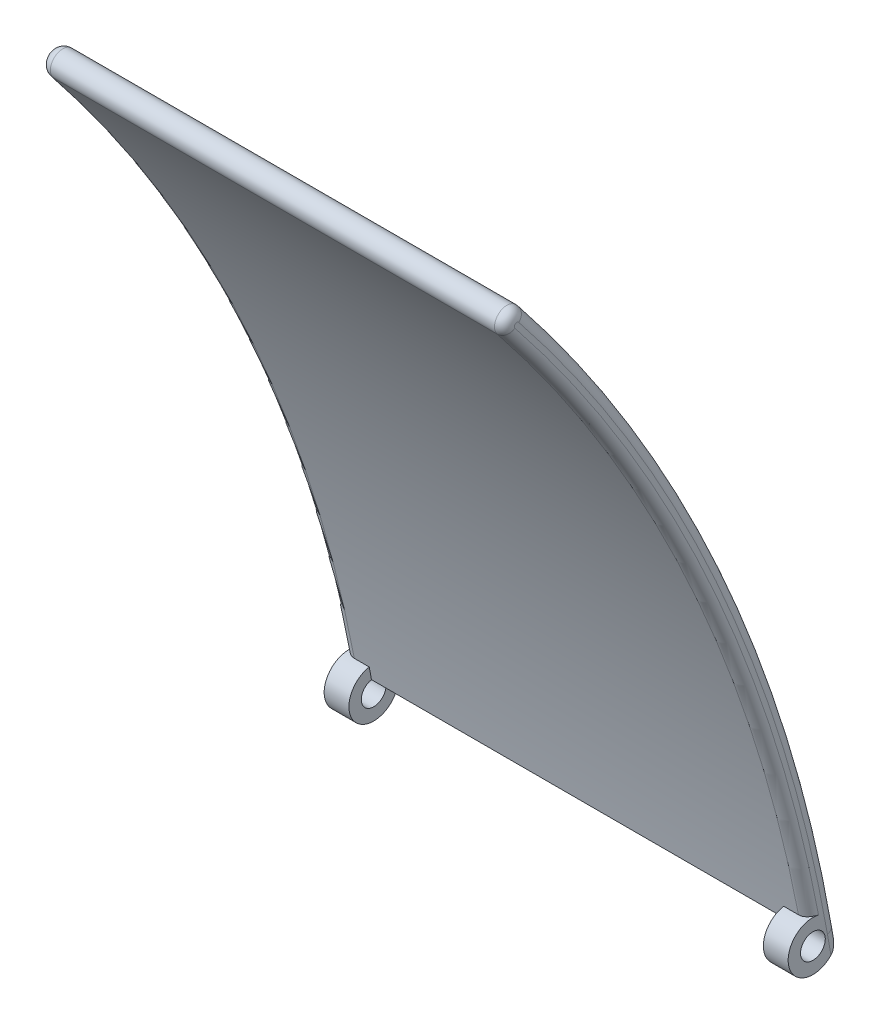
SolidWorks part; units mm, degrees
ref_plane "Front Plane" through (0, 0, 0) normal (0, 0, 1) x (1, 0, 0)
ref_plane "Top Plane" through (0, 0, 0) normal (0, 1, 0) x (1, 0, 0)
ref_plane "Right Plane" through (0, 0, 0) normal (1, 0, 0) x (0, 0, -1)
sketch "Sketch9" plane through (0, 0, 0) normal (1, 0, 0) x (0, 0, -1)
  line L0 (0, 0) -> (-50000, 0) construction
  line L1 (0, 0) -> (0, 50000) construction
  line L2 (0, 0) -> (-0.1736, 0.9848)
  line L3 (-5.0771, 0) -> (-5.0977, 0.1166)
  line L4 (0, 0) -> (-5.0771, 0)
  line L7 (-4.924, -0.8682) -> (-5.0977, 0.1166) construction
  arc A0 (-0.1736, 0.9848) -> (-62.9066, 140) centre (-304.4663, -52.6702) ccw
  arc A1 (-5.0977, 0.1166) -> (-66.8155, 136.8822) centre (-304.4663, -52.6702) ccw
  arc A2 (-66.8155, 136.8822) -> (-62.9066, 140) centre (-64.8611, 138.4411) cw
  point P8 (0, 0)
  dimension "D1" = 10
  dimension "D2" = 1
  dimension "D3" = 140
  dimension "D5" = 66.8155
  dimension "D4" = 5
extrude "Boss-Extrude8" add sketch "Sketch9" along normal mid plane 93.68
sketch "Sketch10" plane through (46.84, 0, 0) normal (1, 0, 0) x (0, 0, -1)
  circle A0 centre (-5.0771, 0) radius 5
  dimension "D1" = 10
extrude "Boss-Extrude9" add sketch "Sketch10" against normal blind 5
mirror "Mirror1" about plane through (0, 0, 0) normal (1, 0, 0) of "Boss-Extrude9"
sketch "Sketch11" plane through (46.84, 0, 0) normal (1, 0, 0) x (0, 0, -1)
  circle A1 centre (-5.0771, 0) radius 2.5
  dimension "D1" = 5
extrude "Cut-Extrude4" cut sketch "Sketch11" against normal through all
fillet "Fillet1" radius 2 8 edges at (-46.84, 0.4924, 0.0868) (-46.84, 74.5879, 28.3986) (-46.84, 140.3956, 66.42) (46.84, 0.4924, 0.0868) (46.84, 74.5879, 28.3986) (46.84, 140.3956, 66.42) (-46.84, 74.4238, 22.8282) (46.84, 74.4238, 22.8282)
